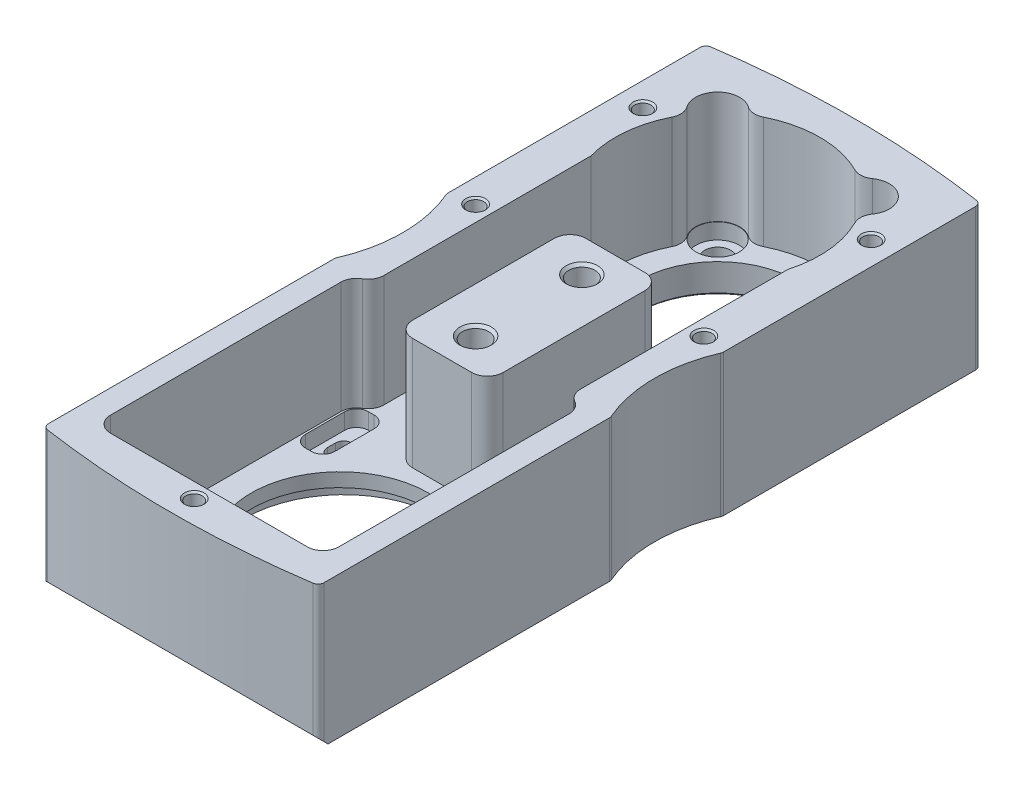
SolidWorks part; units mm, degrees
ref_plane "Front Plane" through (0, 0, 0) normal (0, 0, 1) x (1, 0, 0)
ref_plane "Top Plane" through (0, 0, 0) normal (0, 1, 0) x (1, 0, 0)
ref_plane "Right Plane" through (0, 0, 0) normal (1, 0, 0) x (0, 0, -1)
sketch "Sketch1" plane through (0, 0, 0) normal (0, 1, 0) x (1, 0, 0)
  line L0 (-35, 76.5086) -> (-35, 3.969)
  line L1 (35, 3.969) -> (35, 76.5086)
  line L2 (35, 105.4914) -> (35, 169.531)
  line L3 (-35, 169.531) -> (-35, 105.4914)
  arc A0 (-35, 3.969) -> (-33.7199, 2.4852) centre (-33.5, 3.969) ccw
  arc A1 (-33.7199, 2.4852) -> (33.7199, 2.4852) centre (0, 230) ccw
  arc A2 (33.7199, 2.4852) -> (35, 3.969) centre (33.5, 3.969) ccw
  arc A3 (35, 76.5086) -> (34.8767, 77.1042) centre (33.5, 76.5086) ccw
  arc A4 (34.8767, 77.1042) -> (34.8767, 104.8958) centre (67, 91) cw
  arc A5 (34.8767, 104.8958) -> (35, 105.4914) centre (33.5, 105.4914) ccw
  arc A6 (35, 169.531) -> (33.7199, 171.0148) centre (33.5, 169.531) ccw
  arc A7 (33.7199, 171.0148) -> (-33.7199, 171.0148) centre (0, -56.5) ccw
  arc A8 (-33.7199, 171.0148) -> (-35, 169.531) centre (-33.5, 169.531) ccw
  arc A9 (-35, 105.4914) -> (-34.8767, 104.8958) centre (-33.5, 105.4914) ccw
  arc A10 (-34.8767, 104.8958) -> (-34.8767, 77.1042) centre (-67, 91) cw
  arc A11 (-34.8767, 77.1042) -> (-35, 76.5086) centre (-33.5, 76.5086) ccw
extrude "Boss-Extrude1" add sketch "Sketch1" along normal blind 36
sketch "Sketch2" plane through (0, 0, 0) normal (1, 0, 0) x (0, 0, -1)
  line L0 (0, 5) -> (0, 0)
  line L1 (0, 0) -> (5, 0)
  line L2 (5, 0) -> (0, 5)
extrude "Cut-Extrude1" cut sketch "Sketch2" along normal blind 43 and the other way blind 43
ref_plane "Plane1" through (0, 36, 0) normal (0, 1, 0) x (1, 0, 0)
sketch "Sketch3" plane through (0, 0, 0) normal (1, 0, 0) x (0, 0, -1)
  line L0 (104.5, 36) -> (108.5, 36)
  line L1 (108.5, 36) -> (107.8235, 35.3235)
  line L2 (107.8235, 35.3235) -> (107.8235, 6)
  line L3 (107.8235, 6) -> (104.5, 4.0812)
  line L4 (104.5, 4.0812) -> (104.5, 36)
  line L5 (104.5, 4.0812) -> (104.5, 36) construction
revolve "Cut-Revolve1" cut sketch "Sketch3" angle 360 about L5 reverse direction yes
cosmetic thread "Cosmetic Thread1" parameters "D1"=25, "D2"=8
sketch "Sketch4" plane through (0, 0, 0) normal (1, 0, 0) x (0, 0, -1)
  line L0 (77.5, 36) -> (81.5, 36)
  line L1 (81.5, 36) -> (80.8235, 35.3235)
  line L2 (80.8235, 35.3235) -> (80.8235, 6)
  line L3 (80.8235, 6) -> (77.5, 4.0812)
  line L4 (77.5, 4.0812) -> (77.5, 36)
  line L5 (77.5, 4.0812) -> (77.5, 36) construction
revolve "Cut-Revolve2" cut sketch "Sketch4" angle 360 about L5 reverse direction yes
cosmetic thread "Cosmetic Thread2" parameters "D1"=25, "D2"=8
ref_plane "Plane2" through (-29, 0, 0) normal (1, 0, 0) x (0, 0, -1)
sketch "Sketch5" plane through (-29, 0, 0) normal (1, 0, 0) x (0, 0, -1)
  line L0 (149, 36) -> (151.5, 36)
  line L1 (151.5, 36) -> (151.067, 35.567)
  line L2 (151.067, 35.567) -> (151.067, 18)
  line L3 (151.067, 18) -> (149, 16.8066)
  line L4 (149, 16.8066) -> (149, 36)
  line L5 (149, 16.8066) -> (149, 36) construction
revolve "Cut-Revolve3" cut sketch "Sketch5" angle 360 about L5 reverse direction yes
cosmetic thread "Cosmetic Thread3" parameters "D1"=15, "D2"=5
sketch "Sketch6" plane through (-29, 0, 0) normal (1, 0, 0) x (0, 0, -1)
  line L0 (106.5, 36) -> (109, 36)
  line L1 (109, 36) -> (108.567, 35.567)
  line L2 (108.567, 35.567) -> (108.567, 18)
  line L3 (108.567, 18) -> (106.5, 16.8066)
  line L4 (106.5, 16.8066) -> (106.5, 36)
  line L5 (106.5, 16.8066) -> (106.5, 36) construction
revolve "Cut-Revolve4" cut sketch "Sketch6" angle 360 about L5 reverse direction yes
cosmetic thread "Cosmetic Thread4" parameters "D1"=15, "D2"=5
ref_plane "Plane3" through (29, 0, 0) normal (1, 0, 0) x (0, 0, -1)
sketch "Sketch7" plane through (29, 0, 0) normal (1, 0, 0) x (0, 0, -1)
  line L0 (149, 36) -> (151.5, 36)
  line L1 (151.5, 36) -> (151.067, 35.567)
  line L2 (151.067, 35.567) -> (151.067, 18)
  line L3 (151.067, 18) -> (149, 16.8066)
  line L4 (149, 16.8066) -> (149, 36)
  line L5 (149, 16.8066) -> (149, 36) construction
revolve "Cut-Revolve5" cut sketch "Sketch7" angle 360 about L5 reverse direction yes
cosmetic thread "Cosmetic Thread5" parameters "D1"=15, "D2"=5
sketch "Sketch8" plane through (29, 0, 0) normal (1, 0, 0) x (0, 0, -1)
  line L0 (106.5, 36) -> (109, 36)
  line L1 (109, 36) -> (108.567, 35.567)
  line L2 (108.567, 35.567) -> (108.567, 18)
  line L3 (108.567, 18) -> (106.5, 16.8066)
  line L4 (106.5, 16.8066) -> (106.5, 36)
  line L5 (106.5, 16.8066) -> (106.5, 36) construction
revolve "Cut-Revolve6" cut sketch "Sketch8" angle 360 about L5 reverse direction yes
cosmetic thread "Cosmetic Thread6" parameters "D1"=15, "D2"=5
sketch "Sketch9" plane through (0, 0, 0) normal (1, 0, 0) x (0, 0, -1)
  line L0 (6, 36) -> (8.5, 36)
  line L1 (8.5, 36) -> (8.067, 35.567)
  line L2 (8.067, 35.567) -> (8.067, 18)
  line L3 (8.067, 18) -> (6, 16.8066)
  line L4 (6, 16.8066) -> (6, 36)
  line L5 (6, 16.8066) -> (6, 36) construction
revolve "Cut-Revolve7" cut sketch "Sketch9" angle 360 about L5 reverse direction yes
cosmetic thread "Cosmetic Thread7" parameters "D1"=15, "D2"=5
sketch "Sketch10" plane through (0, 0, 0) normal (1, 0, 0) x (0, 0, -1)
  line L0 (139, 36) -> (159, 36)
  line L1 (159, 36) -> (159, 0.6)
  line L2 (159, 0.6) -> (159.6, 0)
  line L3 (159.6, 0) -> (139, 0)
  line L4 (139, 0) -> (139, 36)
  line L5 (139, 0) -> (139, 36) construction
revolve "Cut-Revolve8" cut sketch "Sketch10" angle 360 about L5 reverse direction yes
ref_plane "Plane4" through (19, 0, 0) normal (1, 0, 0) x (0, 0, -1)
sketch "Sketch11" plane through (19, 0, 0) normal (1, 0, 0) x (0, 0, -1)
  line L0 (120, 36) -> (125.5, 36)
  line L1 (125.5, 36) -> (125.5, 3.5)
  line L2 (125.5, 3.5) -> (123.3, 3.5)
  line L3 (123.3, 3.5) -> (123.3, 0)
  line L4 (123.3, 0) -> (120, 0)
  line L5 (120, 0) -> (120, 36)
  line L6 (120, 0) -> (120, 36) construction
revolve "Cut-Revolve9" cut sketch "Sketch11" angle 360 about L6 reverse direction yes
sketch "Sketch12" plane through (19, 0, 0) normal (1, 0, 0) x (0, 0, -1)
  line L0 (158, 36) -> (163.5, 36)
  line L1 (163.5, 36) -> (163.5, 3.5)
  line L2 (163.5, 3.5) -> (161.3, 3.5)
  line L3 (161.3, 3.5) -> (161.3, 0)
  line L4 (161.3, 0) -> (158, 0)
  line L5 (158, 0) -> (158, 36)
  line L6 (158, 0) -> (158, 36) construction
revolve "Cut-Revolve10" cut sketch "Sketch12" angle 360 about L6 reverse direction yes
ref_plane "Plane5" through (-19, 0, 0) normal (1, 0, 0) x (0, 0, -1)
sketch "Sketch13" plane through (-19, 0, 0) normal (1, 0, 0) x (0, 0, -1)
  line L0 (120, 36) -> (125.5, 36)
  line L1 (125.5, 36) -> (125.5, 3.5)
  line L2 (125.5, 3.5) -> (123.3, 3.5)
  line L3 (123.3, 3.5) -> (123.3, 0)
  line L4 (123.3, 0) -> (120, 0)
  line L5 (120, 0) -> (120, 36)
  line L6 (120, 0) -> (120, 36) construction
revolve "Cut-Revolve11" cut sketch "Sketch13" angle 360 about L6 reverse direction yes
sketch "Sketch14" plane through (-19, 0, 0) normal (1, 0, 0) x (0, 0, -1)
  line L0 (158, 36) -> (163.5, 36)
  line L1 (163.5, 36) -> (163.5, 3.5)
  line L2 (163.5, 3.5) -> (161.3, 3.5)
  line L3 (161.3, 3.5) -> (161.3, 0)
  line L4 (161.3, 0) -> (158, 0)
  line L5 (158, 0) -> (158, 36)
  line L6 (158, 0) -> (158, 36) construction
revolve "Cut-Revolve12" cut sketch "Sketch14" angle 360 about L6 reverse direction yes
sketch "Sketch15" plane through (0, 36, 0) normal (0, 1, 0) x (1, 0, 0)
  line L0 (23.9987, 10.2513) -> (25.4987, 10.2513)
  line L1 (28.4987, 13.2513) -> (28.4987, 23.2513)
  line L2 (25.4987, 26.2513) -> (23.9987, 26.2513)
  line L3 (20.9987, 23.2513) -> (20.9987, 13.2513)
  arc A0 (20.9987, 13.2513) -> (23.9987, 10.2513) centre (23.9987, 13.2513) ccw
  arc A1 (25.4987, 10.2513) -> (28.4987, 13.2513) centre (25.4987, 13.2513) ccw
  arc A2 (28.4987, 23.2513) -> (25.4987, 26.2513) centre (25.4987, 23.2513) ccw
  arc A3 (23.9987, 26.2513) -> (20.9987, 23.2513) centre (23.9987, 23.2513) ccw
extrude "Cut-Extrude2" cut sketch "Sketch15" against normal blind 32.6
sketch "Sketch16" plane through (0, 36, 0) normal (0, 1, 0) x (1, 0, 0)
  line L0 (23.9987, 59.7487) -> (25.4987, 59.7487)
  line L1 (28.4987, 62.7487) -> (28.4987, 72.7487)
  line L2 (25.4987, 75.7487) -> (23.9987, 75.7487)
  line L3 (20.9987, 72.7487) -> (20.9987, 62.7487)
  arc A0 (20.9987, 62.7487) -> (23.9987, 59.7487) centre (23.9987, 62.7487) ccw
  arc A1 (25.4987, 59.7487) -> (28.4987, 62.7487) centre (25.4987, 62.7487) ccw
  arc A2 (28.4987, 72.7487) -> (25.4987, 75.7487) centre (25.4987, 72.7487) ccw
  arc A3 (23.9987, 75.7487) -> (20.9987, 72.7487) centre (23.9987, 72.7487) ccw
extrude "Cut-Extrude3" cut sketch "Sketch16" against normal blind 32.6
sketch "Sketch17" plane through (0, 36, 0) normal (0, 1, 0) x (1, 0, 0)
  line L0 (-25.4987, 59.7487) -> (-23.9987, 59.7487)
  line L1 (-20.9987, 62.7487) -> (-20.9987, 72.7487)
  line L2 (-23.9987, 75.7487) -> (-25.4987, 75.7487)
  line L3 (-28.4987, 72.7487) -> (-28.4987, 62.7487)
  arc A0 (-28.4987, 62.7487) -> (-25.4987, 59.7487) centre (-25.4987, 62.7487) ccw
  arc A1 (-23.9987, 59.7487) -> (-20.9987, 62.7487) centre (-23.9987, 62.7487) ccw
  arc A2 (-20.9987, 72.7487) -> (-23.9987, 75.7487) centre (-23.9987, 72.7487) ccw
  arc A3 (-25.4987, 75.7487) -> (-28.4987, 72.7487) centre (-25.4987, 72.7487) ccw
extrude "Cut-Extrude4" cut sketch "Sketch17" against normal blind 32.6
sketch "Sketch18" plane through (0, 36, 0) normal (0, 1, 0) x (1, 0, 0)
  line L0 (-25.4987, 10.2513) -> (-23.9987, 10.2513)
  line L1 (-20.9987, 13.2513) -> (-20.9987, 23.2513)
  line L2 (-23.9987, 26.2513) -> (-25.4987, 26.2513)
  line L3 (-28.4987, 23.2513) -> (-28.4987, 13.2513)
  arc A0 (-28.4987, 13.2513) -> (-25.4987, 10.2513) centre (-25.4987, 13.2513) ccw
  arc A1 (-23.9987, 10.2513) -> (-20.9987, 13.2513) centre (-23.9987, 13.2513) ccw
  arc A2 (-20.9987, 23.2513) -> (-23.9987, 26.2513) centre (-23.9987, 23.2513) ccw
  arc A3 (-25.4987, 26.2513) -> (-28.4987, 23.2513) centre (-25.4987, 23.2513) ccw
extrude "Cut-Extrude5" cut sketch "Sketch18" against normal blind 32.6
sketch "Sketch19" plane through (0, 36, 0) normal (0, 1, 0) x (1, 0, 0)
  line L0 (26.8987, 17.2513) -> (26.8987, 19.2513)
  line L1 (22.5987, 19.2513) -> (22.5987, 17.2513)
  arc A0 (22.5987, 17.2513) -> (26.8987, 17.2513) centre (24.7487, 17.2513) ccw
  arc A1 (26.8987, 19.2513) -> (22.5987, 19.2513) centre (24.7487, 19.2513) ccw
extrude "Cut-Extrude6" cut sketch "Sketch19" against normal blind 36
sketch "Sketch20" plane through (0, 36, 0) normal (0, 1, 0) x (1, 0, 0)
  line L0 (26.8987, 66.7487) -> (26.8987, 68.7487)
  line L1 (22.5987, 68.7487) -> (22.5987, 66.7487)
  arc A0 (22.5987, 66.7487) -> (26.8987, 66.7487) centre (24.7487, 66.7487) ccw
  arc A1 (26.8987, 68.7487) -> (22.5987, 68.7487) centre (24.7487, 68.7487) ccw
extrude "Cut-Extrude7" cut sketch "Sketch20" against normal blind 36
sketch "Sketch21" plane through (0, 36, 0) normal (0, 1, 0) x (1, 0, 0)
  line L0 (-22.5987, 66.7487) -> (-22.5987, 68.7487)
  line L1 (-26.8987, 68.7487) -> (-26.8987, 66.7487)
  arc A0 (-26.8987, 66.7487) -> (-22.5987, 66.7487) centre (-24.7487, 66.7487) ccw
  arc A1 (-22.5987, 68.7487) -> (-26.8987, 68.7487) centre (-24.7487, 68.7487) ccw
extrude "Cut-Extrude8" cut sketch "Sketch21" against normal blind 36
sketch "Sketch22" plane through (0, 36, 0) normal (0, 1, 0) x (1, 0, 0)
  line L0 (-22.5987, 17.2513) -> (-22.5987, 19.2513)
  line L1 (-26.8987, 19.2513) -> (-26.8987, 17.2513)
  arc A0 (-26.8987, 17.2513) -> (-22.5987, 17.2513) centre (-24.7487, 17.2513) ccw
  arc A1 (-22.5987, 19.2513) -> (-26.8987, 19.2513) centre (-24.7487, 19.2513) ccw
extrude "Cut-Extrude9" cut sketch "Sketch22" against normal blind 36
sketch "Sketch23" plane through (0, 0, 0) normal (0, 1, 0) x (1, 0, 0)
  line L0 (25.25, 42) -> (25.25, 44)
  line L1 (-25.25, 44) -> (-25.25, 42)
  arc A0 (-25.25, 42) -> (25.25, 42) centre (0, 42) ccw
  arc A1 (25.25, 44) -> (-25.25, 44) centre (0, 44) ccw
extrude "Cut-Extrude10" cut sketch "Sketch23" along normal blind 4
sketch "Sketch24" plane through (0, 0, 0) normal (1, 0, 0) x (0, 0, -1)
  line L0 (43, 36) -> (65.5, 36)
  line L1 (65.5, 36) -> (65.5, 0)
  line L2 (65.5, 0) -> (43, 0)
  line L3 (43, 0) -> (43, 36)
  line L4 (43, 0) -> (43, 36) construction
revolve "Cut-Revolve13" cut sketch "Sketch24" angle 360 about L4 reverse direction yes
sketch "Sketch25" plane through (0, 36, 0) normal (0, 1, 0) x (1, 0, 0)
  line L0 (-24.9987, 9.7513) -> (24.9987, 9.7513)
  line L1 (28.9987, 13.7513) -> (28.9987, 72.2487)
  line L2 (25, 79.1762) -> (25, 131.8586)
  line L3 (-25, 131.8586) -> (-25, 79.1762)
  line L4 (-28.9987, 72.2487) -> (-28.9987, 13.7513)
  line L5 (-11.5, 109) -> (-11.5, 73)
  line L6 (-7.5, 69) -> (7.5, 69)
  line L7 (11.5, 73) -> (11.5, 109)
  line L8 (7.5, 113) -> (-7.5, 113)
  arc A0 (-28.9987, 13.7513) -> (-24.9987, 9.7513) centre (-24.9987, 13.7513) ccw
  arc A1 (24.9987, 9.7513) -> (28.9987, 13.7513) centre (24.9987, 13.7513) ccw
  arc A2 (28.9987, 72.2487) -> (26.9994, 75.7125) centre (24.9987, 72.2487) ccw
  arc A3 (26.9994, 75.7125) -> (25, 79.1762) centre (29, 79.1762) cw
  arc A4 (25, 131.8586) -> (23.2467, 150.6444) centre (0, 139) ccw
  arc A5 (23.2467, 150.6444) -> (23.5635, 154.7543) centre (26.8231, 152.4359) cw
  arc A6 (23.5635, 154.7543) -> (15.7543, 162.5635) centre (19, 158) ccw
  arc A7 (15.7543, 162.5635) -> (11.6444, 162.2467) centre (13.4359, 165.8231) cw
  arc A8 (11.6444, 162.2467) -> (-11.6444, 162.2467) centre (0, 139) ccw
  arc A9 (-11.6444, 162.2467) -> (-15.7543, 162.5635) centre (-13.4359, 165.8231) cw
  arc A10 (-15.7543, 162.5635) -> (-23.5635, 154.7543) centre (-19, 158) ccw
  arc A11 (-23.5635, 154.7543) -> (-23.2467, 150.6444) centre (-26.8231, 152.4359) cw
  arc A12 (-23.2467, 150.6444) -> (-25, 131.8586) centre (0, 139) ccw
  arc A13 (-25, 79.1762) -> (-26.9994, 75.7125) centre (-29, 79.1762) cw
  arc A14 (-26.9994, 75.7125) -> (-28.9987, 72.2487) centre (-24.9987, 72.2487) ccw
  arc A15 (-11.5, 73) -> (-7.5, 69) centre (-7.5, 73) ccw
  arc A16 (7.5, 69) -> (11.5, 73) centre (7.5, 73) ccw
  arc A17 (11.5, 109) -> (7.5, 113) centre (7.5, 109) ccw
  arc A18 (-7.5, 113) -> (-11.5, 109) centre (-7.5, 109) ccw
extrude "Cut-Extrude11" cut sketch "Sketch25" against normal blind 28.5
ref_plane "Plane6" through (0, 3.4, 0) normal (0, 1, 0) x (1, 0, 0)
ref_plane "Plane7" through (0, 3.5, 0) normal (0, 1, 0) x (1, 0, 0)
ref_plane "Plane8" through (0, 0, 0) normal (0, 1, 0) x (1, 0, 0)
ref_plane "Plane9" through (0, -8, 0) normal (0, 1, 0) x (1, 0, 0)
ref_plane "Plane10" through (0, 8.5, 0) normal (0, 1, 0) x (1, 0, 0)
ref_plane "Plane11" through (0, 8.5, 0) normal (0, 1, 0) x (1, 0, 0)
ref_plane "ANBAU XY" through (0, 0, 0) normal (0, 1, 0) x (1, 0, 0)
ref_plane "ANBAU XZ" through (0, 0, -139) normal (0, 0, 1) x (1, 0, 0)
ref_plane "ANBAU YZ" through (0, 0, 0) normal (1, 0, 0) x (0, 0, -1)
ref_axis "ANBAU X" through (-80.9, 0, -139) along (1, 0, 0)
ref_axis "ANBAU Y" through (0, 0, 50) along (0, 0, -1)
ref_axis "ANBAU Z" through (0, 50, -139) along (0, -1, 0)
sketch3d "ANBAU"
  point P0 (0, 0, -139)
ref_plane "AS 1 XY" through (0, 3.5, 0) normal (0, 1, 0) x (1, 0, 0)
ref_plane "AS 1 XZ" through (0, 0, -120) normal (0, 0, 1) x (1, 0, 0)
ref_plane "AS 1 YZ" through (19, 0, 0) normal (1, 0, 0) x (0, 0, -1)
ref_axis "AS 1 X" through (-80.9, 3.5, -120) along (1, 0, 0)
ref_axis "AS 1 Y" through (19, 3.5, 50) along (0, 0, -1)
ref_axis "AS 1 Z" through (19, 50, -120) along (0, -1, 0)
sketch3d "AS 1"
  point P0 (19, 3.5, -120)
ref_plane "AS 2 XY" through (0, 3.5, 0) normal (0, 1, 0) x (1, 0, 0)
ref_plane "AS 2 XZ" through (0, 0, -158) normal (0, 0, 1) x (1, 0, 0)
ref_plane "AS 2 YZ" through (19, 0, 0) normal (1, 0, 0) x (0, 0, -1)
ref_axis "AS 2 X" through (-80.9, 3.5, -158) along (1, 0, 0)
ref_axis "AS 2 Y" through (19, 3.5, 50) along (0, 0, -1)
ref_axis "AS 2 Z" through (19, 50, -158) along (0, -1, 0)
sketch3d "AS 2"
  point P0 (19, 3.5, -158)
ref_plane "AS 3 XY" through (0, 3.5, 0) normal (0, 1, 0) x (1, 0, 0)
ref_plane "AS 3 XZ" through (0, 0, -120) normal (0, 0, 1) x (1, 0, 0)
ref_plane "AS 3 YZ" through (-19, 0, 0) normal (1, 0, 0) x (0, 0, -1)
ref_axis "AS 3 X" through (-80.9, 3.5, -120) along (1, 0, 0)
ref_axis "AS 3 Y" through (-19, 3.5, 50) along (0, 0, -1)
ref_axis "AS 3 Z" through (-19, 50, -120) along (0, -1, 0)
sketch3d "AS 3"
  point P0 (-19, 3.5, -120)
ref_plane "AS 4 XY" through (0, 3.5, 0) normal (0, 1, 0) x (1, 0, 0)
ref_plane "AS 4 XZ" through (0, 0, -158) normal (0, 0, 1) x (1, 0, 0)
ref_plane "AS 4 YZ" through (-19, 0, 0) normal (1, 0, 0) x (0, 0, -1)
ref_axis "AS 4 X" through (-80.9, 3.5, -158) along (1, 0, 0)
ref_axis "AS 4 Y" through (-19, 3.5, 50) along (0, 0, -1)
ref_axis "AS 4 Z" through (-19, 50, -158) along (0, -1, 0)
sketch3d "AS 4"
  point P0 (-19, 3.5, -158)
ref_plane "DM XY" through (0, 0, 0) normal (0, 1, 0) x (1, 0, 0)
ref_plane "DM XZ" through (0, 0, -43) normal (0, 0, 1) x (1, 0, 0)
ref_plane "DM YZ" through (0, 0, 0) normal (1, 0, 0) x (0, 0, -1)
ref_axis "DM X" through (-80.9, 0, -43) along (1, 0, 0)
ref_axis "DM Y" through (0, 0, 50) along (0, 0, -1)
ref_axis "DM Z" through (0, 50, -43) along (0, -1, 0)
sketch3d "DM"
  point P0 (0, 0, -43)
ref_plane "MS 1 XY" through (0, -8, 0) normal (0, 1, 0) x (1, 0, 0)
ref_plane "MS 1 XZ" through (0, 0, -18.2513) normal (0, 0, 1) x (1, 0, 0)
ref_plane "MS 1 YZ" through (24.7487, 0, 0) normal (1, 0, 0) x (0, 0, -1)
ref_axis "MS 1 X" through (-80.9, -8, -18.2513) along (1, 0, 0)
ref_axis "MS 1 Y" through (24.7487, -8, 50) along (0, 0, -1)
ref_axis "MS 1 Z" through (24.7487, 50, -18.2513) along (0, -1, 0)
sketch3d "MS 1"
  point P0 (24.7487, -8, -18.2513)
ref_plane "MS 2 XY" through (0, -8, 0) normal (0, 1, 0) x (1, 0, 0)
ref_plane "MS 2 XZ" through (0, 0, -67.7487) normal (0, 0, 1) x (1, 0, 0)
ref_plane "MS 2 YZ" through (24.7487, 0, 0) normal (1, 0, 0) x (0, 0, -1)
ref_axis "MS 2 X" through (-80.9, -8, -67.7487) along (1, 0, 0)
ref_axis "MS 2 Y" through (24.7487, -8, 50) along (0, 0, -1)
ref_axis "MS 2 Z" through (24.7487, 50, -67.7487) along (0, -1, 0)
sketch3d "MS 2"
  point P0 (24.7487, -8, -67.7487)
ref_plane "MS 3 XY" through (0, -8, 0) normal (0, 1, 0) x (1, 0, 0)
ref_plane "MS 3 XZ" through (0, 0, -67.7487) normal (0, 0, 1) x (1, 0, 0)
ref_plane "MS 3 YZ" through (-24.7487, 0, 0) normal (1, 0, 0) x (0, 0, -1)
ref_axis "MS 3 X" through (-80.9, -8, -67.7487) along (1, 0, 0)
ref_axis "MS 3 Y" through (-24.7487, -8, 50) along (0, 0, -1)
ref_axis "MS 3 Z" through (-24.7487, 50, -67.7487) along (0, -1, 0)
sketch3d "MS 3"
  point P0 (-24.7487, -8, -67.7487)
ref_plane "MS 4 XY" through (0, -8, 0) normal (0, 1, 0) x (1, 0, 0)
ref_plane "MS 4 XZ" through (0, 0, -18.2513) normal (0, 0, 1) x (1, 0, 0)
ref_plane "MS 4 YZ" through (-24.7487, 0, 0) normal (1, 0, 0) x (0, 0, -1)
ref_axis "MS 4 X" through (-80.9, -8, -18.2513) along (1, 0, 0)
ref_axis "MS 4 Y" through (-24.7487, -8, 50) along (0, 0, -1)
ref_axis "MS 4 Z" through (-24.7487, 50, -18.2513) along (0, -1, 0)
sketch3d "MS 4"
  point P0 (-24.7487, -8, -18.2513)
ref_plane "NABE_AXIS XY" through (0, 8.5, 0) normal (0, 1, 0) x (1, 0, 0)
ref_plane "NABE_AXIS XZ" through (0, 0, -139) normal (0, 0, 1) x (1, 0, 0)
ref_plane "NABE_AXIS YZ" through (0, 0, 0) normal (1, 0, 0) x (0, 0, -1)
ref_axis "NABE_AXIS X" through (-80.9, 8.5, -139) along (1, 0, 0)
ref_axis "NABE_AXIS Y" through (0, 8.5, 50) along (0, 0, -1)
ref_axis "NABE_AXIS Z" through (0, 50, -139) along (0, -1, 0)
sketch3d "NABE_AXIS"
  point P0 (0, 8.5, -139)
ref_plane "NABE_MOT XY" through (0, 8.5, 0) normal (0, 1, 0) x (1, 0, 0)
ref_plane "NABE_MOT XZ" through (0, 0, -43) normal (0, 0, 1) x (1, 0, 0)
ref_plane "NABE_MOT YZ" through (0, 0, 0) normal (1, 0, 0) x (0, 0, -1)
ref_axis "NABE_MOT X" through (-80.9, 8.5, -43) along (1, 0, 0)
ref_axis "NABE_MOT Y" through (0, 8.5, 50) along (0, 0, -1)
ref_axis "NABE_MOT Z" through (0, 50, -43) along (0, -1, 0)
sketch3d "NABE_MOT"
  point P0 (0, 8.5, -43)
ref_plane "OBERTEIL XY" through (0, 36, 0) normal (0, 1, 0) x (1, 0, 0)
ref_plane "OBERTEIL XZ" through (0, 0, -139) normal (0, 0, 1) x (1, 0, 0)
ref_plane "OBERTEIL YZ" through (0, 0, 0) normal (1, 0, 0) x (0, 0, -1)
ref_axis "OBERTEIL X" through (-80.9, 36, -139) along (1, 0, 0)
ref_axis "OBERTEIL Y" through (0, 36, 50) along (0, 0, -1)
ref_axis "OBERTEIL Z" through (0, 50, -139) along (0, -1, 0)
sketch3d "OBERTEIL"
  point P0 (0, 36, -139)
ref_plane "VM 1 XY" through (0, 3.4, 0) normal (0, 1, 0) x (1, 0, 0)
ref_plane "VM 1 XZ" through (0, 0, -18.2513) normal (0, 0, 1) x (1, 0, 0)
ref_plane "VM 1 YZ" through (24.7487, 0, 0) normal (1, 0, 0) x (0, 0, -1)
ref_axis "VM 1 X" through (-80.9, 3.4, -18.2513) along (1, 0, 0)
ref_axis "VM 1 Y" through (24.7487, 3.4, 50) along (0, 0, -1)
ref_axis "VM 1 Z" through (24.7487, 50, -18.2513) along (0, -1, 0)
sketch3d "VM 1"
  point P0 (24.7487, 3.4, -18.2513)
ref_plane "VM 2 XY" through (0, 3.4, 0) normal (0, 1, 0) x (1, 0, 0)
ref_plane "VM 2 XZ" through (0, 0, -67.7487) normal (0, 0, 1) x (1, 0, 0)
ref_plane "VM 2 YZ" through (24.7487, 0, 0) normal (1, 0, 0) x (0, 0, -1)
ref_axis "VM 2 X" through (-80.9, 3.4, -67.7487) along (1, 0, 0)
ref_axis "VM 2 Y" through (24.7487, 3.4, 50) along (0, 0, -1)
ref_axis "VM 2 Z" through (24.7487, 50, -67.7487) along (0, -1, 0)
sketch3d "VM 2"
  point P0 (24.7487, 3.4, -67.7487)
ref_plane "VM 3 XY" through (0, 3.4, 0) normal (0, 1, 0) x (1, 0, 0)
ref_plane "VM 3 XZ" through (0, 0, -67.7487) normal (0, 0, 1) x (1, 0, 0)
ref_plane "VM 3 YZ" through (-24.7487, 0, 0) normal (1, 0, 0) x (0, 0, -1)
ref_axis "VM 3 X" through (-80.9, 3.4, -67.7487) along (1, 0, 0)
ref_axis "VM 3 Y" through (-24.7487, 3.4, 50) along (0, 0, -1)
ref_axis "VM 3 Z" through (-24.7487, 50, -67.7487) along (0, -1, 0)
sketch3d "VM 3"
  point P0 (-24.7487, 3.4, -67.7487)
ref_plane "VM 4 XY" through (0, 3.4, 0) normal (0, 1, 0) x (1, 0, 0)
ref_plane "VM 4 XZ" through (0, 0, -18.2513) normal (0, 0, 1) x (1, 0, 0)
ref_plane "VM 4 YZ" through (-24.7487, 0, 0) normal (1, 0, 0) x (0, 0, -1)
ref_axis "VM 4 X" through (-80.9, 3.4, -18.2513) along (1, 0, 0)
ref_axis "VM 4 Y" through (-24.7487, 3.4, 50) along (0, 0, -1)
ref_axis "VM 4 Z" through (-24.7487, 50, -18.2513) along (0, -1, 0)
sketch3d "VM 4"
  point P0 (-24.7487, 3.4, -18.2513)
ref_plane "VM_1 1 XY" through (0, 3.4, 0) normal (0, 1, 0) x (1, 0, 0)
ref_plane "VM_1 1 XZ" through (0, 0, -18.2513) normal (0, 0, 1) x (1, 0, 0)
ref_plane "VM_1 1 YZ" through (24.7487, 0, 0) normal (1, 0, 0) x (0, 0, -1)
ref_axis "VM_1 1 X" through (-80.9, 3.4, -18.2513) along (1, 0, 0)
ref_axis "VM_1 1 Y" through (24.7487, 3.4, 50) along (0, 0, -1)
ref_axis "VM_1 1 Z" through (24.7487, 50, -18.2513) along (0, -1, 0)
sketch3d "VM_1 1"
  point P0 (24.7487, 3.4, -18.2513)
ref_plane "VM_1 2 XY" through (0, 3.4, 0) normal (0, 1, 0) x (1, 0, 0)
ref_plane "VM_1 2 XZ" through (0, 0, -67.7487) normal (0, 0, 1) x (1, 0, 0)
ref_plane "VM_1 2 YZ" through (24.7487, 0, 0) normal (1, 0, 0) x (0, 0, -1)
ref_axis "VM_1 2 X" through (-80.9, 3.4, -67.7487) along (1, 0, 0)
ref_axis "VM_1 2 Y" through (24.7487, 3.4, 50) along (0, 0, -1)
ref_axis "VM_1 2 Z" through (24.7487, 50, -67.7487) along (0, -1, 0)
sketch3d "VM_1 2"
  point P0 (24.7487, 3.4, -67.7487)
ref_plane "VM_1 3 XY" through (0, 3.4, 0) normal (0, 1, 0) x (1, 0, 0)
ref_plane "VM_1 3 XZ" through (0, 0, -67.7487) normal (0, 0, 1) x (1, 0, 0)
ref_plane "VM_1 3 YZ" through (-24.7487, 0, 0) normal (1, 0, 0) x (0, 0, -1)
ref_axis "VM_1 3 X" through (-80.9, 3.4, -67.7487) along (1, 0, 0)
ref_axis "VM_1 3 Y" through (-24.7487, 3.4, 50) along (0, 0, -1)
ref_axis "VM_1 3 Z" through (-24.7487, 50, -67.7487) along (0, -1, 0)
sketch3d "VM_1 3"
  point P0 (-24.7487, 3.4, -67.7487)
ref_plane "VM_1 4 XY" through (0, 3.4, 0) normal (0, 1, 0) x (1, 0, 0)
ref_plane "VM_1 4 XZ" through (0, 0, -18.2513) normal (0, 0, 1) x (1, 0, 0)
ref_plane "VM_1 4 YZ" through (-24.7487, 0, 0) normal (1, 0, 0) x (0, 0, -1)
ref_axis "VM_1 4 X" through (-80.9, 3.4, -18.2513) along (1, 0, 0)
ref_axis "VM_1 4 Y" through (-24.7487, 3.4, 50) along (0, 0, -1)
ref_axis "VM_1 4 Z" through (-24.7487, 50, -18.2513) along (0, -1, 0)
sketch3d "VM_1 4"
  point P0 (-24.7487, 3.4, -18.2513)
ref_plane "ZR XY" through (0, 0, 0) normal (0, 1, 0) x (1, 0, 0)
ref_plane "ZR XZ" through (0, 0, -139) normal (0, 0, 1) x (1, 0, 0)
ref_plane "ZR YZ" through (0, 0, 0) normal (1, 0, 0) x (0, 0, -1)
ref_axis "ZR X" through (-80.9, 0, -139) along (1, 0, 0)
ref_axis "ZR Y" through (0, 0, 50) along (0, 0, -1)
ref_axis "ZR Z" through (0, 50, -139) along (0, -1, 0)
sketch3d "ZR"
  point P0 (0, 0, -139)
ref_plane "to_sleeve 1 XY" through (0, -8, 0) normal (0, 1, 0) x (1, 0, 0)
ref_plane "to_sleeve 1 XZ" through (0, 0, -18.2513) normal (0, 0, 1) x (1, 0, 0)
ref_plane "to_sleeve 1 YZ" through (24.7487, 0, 0) normal (1, 0, 0) x (0, 0, -1)
ref_axis "to_sleeve 1 X" through (-80.9, -8, -18.2513) along (1, 0, 0)
ref_axis "to_sleeve 1 Y" through (24.7487, -8, 50) along (0, 0, -1)
ref_axis "to_sleeve 1 Z" through (24.7487, 50, -18.2513) along (0, -1, 0)
sketch3d "to_sleeve 1"
  point P0 (24.7487, -8, -18.2513)
ref_plane "to_sleeve 2 XY" through (0, -8, 0) normal (0, 1, 0) x (1, 0, 0)
ref_plane "to_sleeve 2 XZ" through (0, 0, -67.7487) normal (0, 0, 1) x (1, 0, 0)
ref_plane "to_sleeve 2 YZ" through (24.7487, 0, 0) normal (1, 0, 0) x (0, 0, -1)
ref_axis "to_sleeve 2 X" through (-80.9, -8, -67.7487) along (1, 0, 0)
ref_axis "to_sleeve 2 Y" through (24.7487, -8, 50) along (0, 0, -1)
ref_axis "to_sleeve 2 Z" through (24.7487, 50, -67.7487) along (0, -1, 0)
sketch3d "to_sleeve 2"
  point P0 (24.7487, -8, -67.7487)
ref_plane "to_sleeve 3 XY" through (0, -8, 0) normal (0, 1, 0) x (1, 0, 0)
ref_plane "to_sleeve 3 XZ" through (0, 0, -67.7487) normal (0, 0, 1) x (1, 0, 0)
ref_plane "to_sleeve 3 YZ" through (-24.7487, 0, 0) normal (1, 0, 0) x (0, 0, -1)
ref_axis "to_sleeve 3 X" through (-80.9, -8, -67.7487) along (1, 0, 0)
ref_axis "to_sleeve 3 Y" through (-24.7487, -8, 50) along (0, 0, -1)
ref_axis "to_sleeve 3 Z" through (-24.7487, 50, -67.7487) along (0, -1, 0)
sketch3d "to_sleeve 3"
  point P0 (-24.7487, -8, -67.7487)
ref_plane "to_sleeve 4 XY" through (0, -8, 0) normal (0, 1, 0) x (1, 0, 0)
ref_plane "to_sleeve 4 XZ" through (0, 0, -18.2513) normal (0, 0, 1) x (1, 0, 0)
ref_plane "to_sleeve 4 YZ" through (-24.7487, 0, 0) normal (1, 0, 0) x (0, 0, -1)
ref_axis "to_sleeve 4 X" through (-80.9, -8, -18.2513) along (1, 0, 0)
ref_axis "to_sleeve 4 Y" through (-24.7487, -8, 50) along (0, 0, -1)
ref_axis "to_sleeve 4 Z" through (-24.7487, 50, -18.2513) along (0, -1, 0)
sketch3d "to_sleeve 4"
  point P0 (-24.7487, -8, -18.2513)
other "Freeze***"
